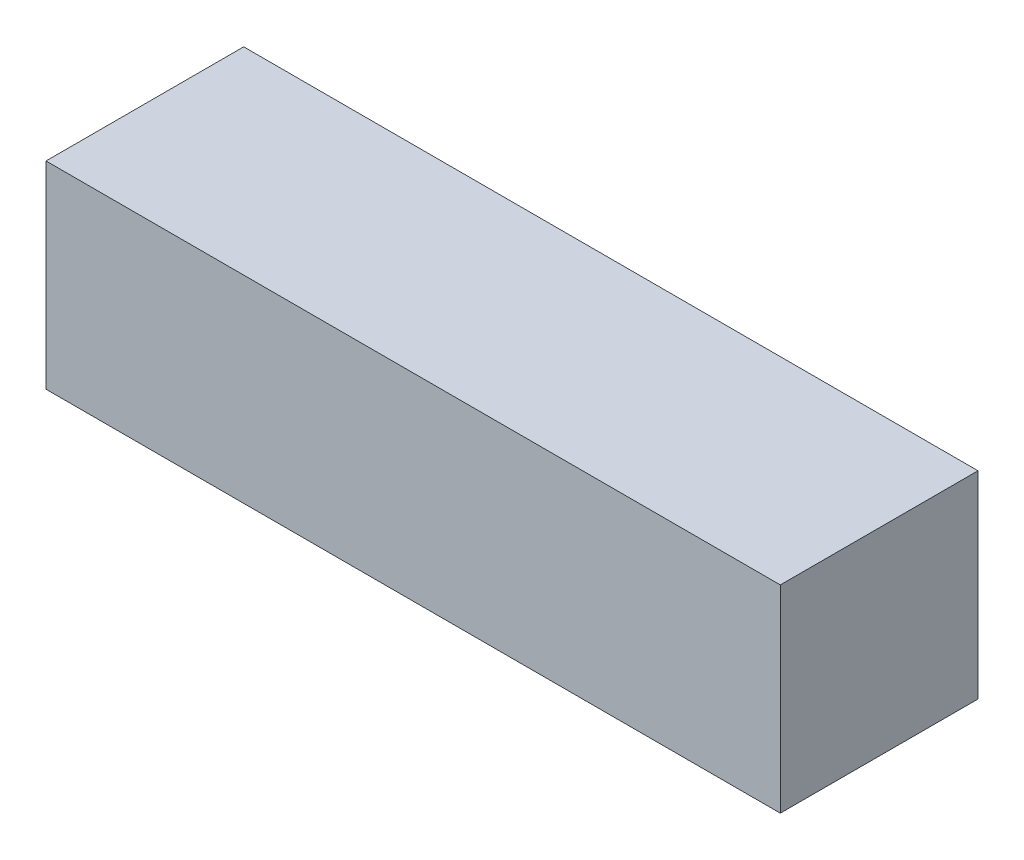
SolidWorks part; units mm, degrees
ref_plane "前视基准面" through (0, 0, 0) normal (0, 0, 1) x (1, 0, 0)
ref_plane "上视基准面" through (0, 0, 0) normal (0, 1, 0) x (1, 0, 0)
ref_plane "右视基准面" through (0, 0, 0) normal (1, 0, 0) x (0, 0, -1)
other "Configuration Table"
sketch "草图1" plane through (0, 0, 0) normal (0, 0, 1) x (1, 0, 0)
  line L1 (-130, -35) -> (130, -35)
  line L2 (-130, -35) -> (-130, 35)
  line L3 (-130, 35) -> (130, 35)
  line L4 (130, -35) -> (130, 35)
  line L5 (-130, -35) -> (130, 35) construction
  line L6 (-130, 35) -> (130, -35) construction
  point P0 (0, 0)
extrude "凸台-拉伸1" add sketch "草图1" along normal blind 70
